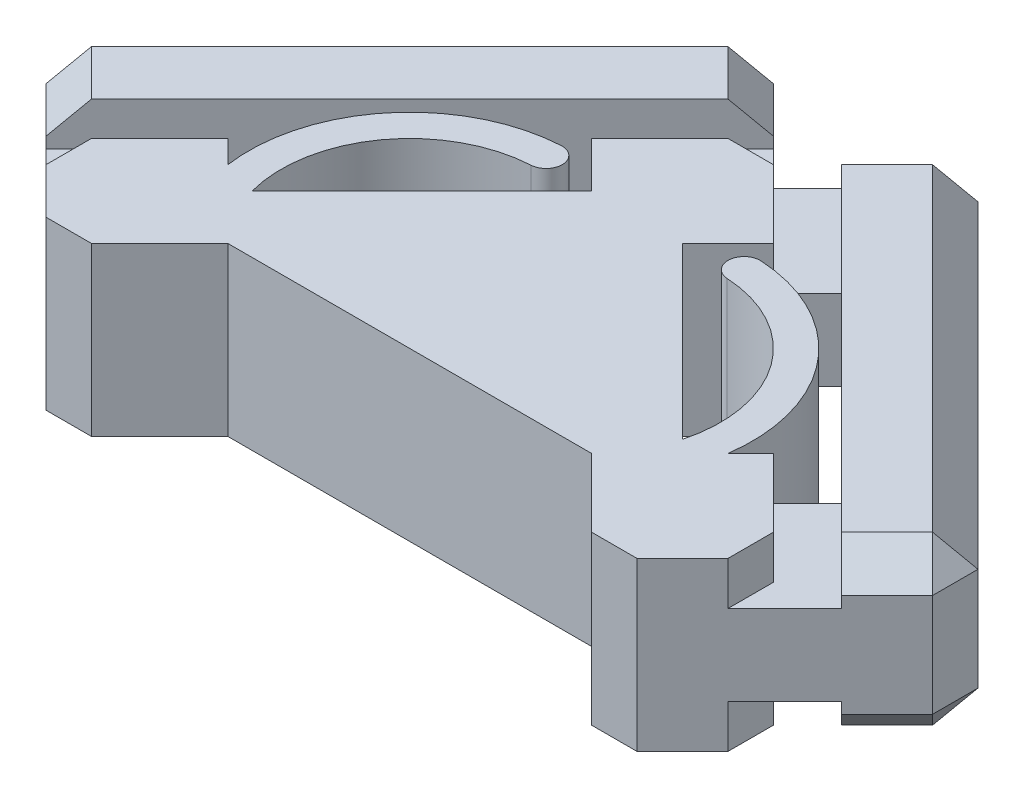
SolidWorks part; units mm, degrees
ref_plane "Front Plane" through (0, 0, 0) normal (0, 0, 1) x (1, 0, 0)
ref_plane "Top Plane" through (0, 0, 0) normal (0, 1, 0) x (1, 0, 0)
ref_plane "Right Plane" through (0, 0, 0) normal (1, 0, 0) x (0, 0, -1)
sketch "Sketch1" plane through (0, 0, 0) normal (0, 1, 0) x (1, 0, 0)
  line L0 (0, 0) -> (-2.8284, -2.8284)
  line L1 (-11.3137, -11.3137) -> (-8.4853, -14.1421)
  line L2 (-8.4853, -14.1421) -> (-5.6569, -11.3137)
  line L3 (-5.6569, -11.3137) -> (5.6569, -11.3137)
  line L4 (5.6569, -11.3137) -> (8.4853, -14.1421)
  line L5 (8.4853, -14.1421) -> (11.3137, -11.3137)
  line L6 (11.3137, -11.3137) -> (8.4853, -8.4853)
  line L7 (1.4142, -4.2426) -> (7.0711, -9.8995)
  line L8 (1.4142, -4.2426) -> (2.8284, -2.8284)
  line L9 (7.0711, -9.8995) -> (8.4853, -8.4853)
  line L10 (-8.4853, -8.4853) -> (-11.3137, -11.3137)
  line L11 (-7.0711, -9.8995) -> (-1.4142, -4.2426)
  line L12 (-7.0711, -9.8995) -> (-8.4853, -8.4853)
  line L13 (-1.4142, -4.2426) -> (-2.8284, -2.8284)
  line L15 (2.8284, -2.8284) -> (0, 0)
  dimension "D1" = 135
  dimension "D2" = 2
  dimension "D3" = 8
  dimension "D4" = 4
  dimension "D5" = 16
extrude "Boss-Extrude1" add sketch "Sketch1" along normal mid plane 5.2
ref_plane "Plane1" through (-5.6569, 0, 5.6569) normal (-0.7071, 0, 0.7071) x (0.7071, 0, 0.7071)
sketch "Sketch2" plane through (-11.3137, 0, 11.3137) normal (-0.7071, 0, 0.7071) x (0.7071, 0, 0.7071)
  line L0 (-1.5, -1.25) -> (-1.5, -2.6)
  line L1 (-4.5, 2.6) -> (-1.5, 2.6)
  line L2 (-4.5, 2.6) -> (-4.5, -2.6)
  line L3 (-4.5, -2.6) -> (-1.5, -2.6)
  line L4 (-1.5, 2.6) -> (-1.5, 1.25)
  line L5 (-1.5, 1.25) -> (0, 1.25)
  line L6 (0, 2.6) -> (0, -2.6) construction
  line L7 (-1.5, -1.25) -> (0, -1.25)
  line L8 (0, 1.25) -> (0, -1.25)
  line L9 (0, 2.6) -> (4, 2.6) construction
  line L10 (0, -2.6) -> (4, -2.6) construction
  point P6 (0, 0)
  dimension "D1" = 2.5
  dimension "D2" = 1.5
  dimension "D3" = 3
extrude "Boss-Extrude2" add sketch "Sketch2" against normal blind 4
mirror "Mirror1" about plane through (-5.6569, 0, 5.6569) normal (-0.7071, 0, 0.7071) of "Boss-Extrude2"
sketch "Sketch3" plane through (-2.8284, 0, 2.8284) normal (-0.7071, 0, 0.7071) x (0.7071, 0, 0.7071)
  line L1 (-4.5, 2.6) -> (-1.5, 2.6)
  line L2 (-4.5, 2.6) -> (-4.5, -2.6)
  line L3 (-4.5, -2.6) -> (-1.5, -2.6)
  line L4 (-1.5, 2.6) -> (-1.5, -2.6)
extrude "Boss-Extrude3" add sketch "Sketch3" along normal blind 8
sketch "Sketch4" plane through (0, 0, 0) normal (0, 1, 0) x (1, 0, 0)
  line L0 (-7.7782, -9.1924) -> (-7.0711, -9.8995)
  line L1 (-7.0711, -9.8995) -> (-6.6921, -9.5206)
  line L2 (-7.0711, -9.8995) -> (-8.4853, -8.4853) construction
  line L3 (-1.4142, -4.2426) -> (-7.0711, -9.8995) construction
  line L4 (-2.8284, -8.4853) -> (-6.7175, -4.5962) construction
  line L5 (-1.0607, 1.0607) -> (-12.3744, -10.253) construction
  line L6 (-2.8284, -2.8284) -> (-1.4142, -4.2426) construction
  arc A0 (-7.7782, -9.1924) -> (-3.1066, -3.493) centre (-2.8284, -8.4853) cw
  arc A1 (-3.1066, -3.493) -> (-3.051, -4.4915) centre (-3.0788, -3.9923) cw
  arc A2 (-6.6921, -9.5206) -> (-3.051, -4.4915) centre (-2.8284, -8.4853) cw
  point P16 (-6.7175, -4.5962)
  dimension "D1" = 5
  dimension "D3" = 1
  dimension "D2" = 0.5
  dimension "D4" = 2
extrude "Boss-Extrude4" add sketch "Sketch4" along normal mid plane 5.2
chamfer "Chamfer1" distance 1 angle 45 8 edges at (-8.8388, -2.6, 2.4749) (-2.1213, -2.6, -2.1213) (-3.182, 0, -3.182) (-2.1213, 2.6, -2.1213) (-8.8388, 2.6, 2.4749) (-13.435, -2.6, 9.1924) (-14.4957, 0, 8.1317) (-13.435, 2.6, 9.1924)
mirror "Mirror2" about plane through (0, 0, 0) normal (1, 0, 0) of "Boss-Extrude4", "Chamfer1", "Mirror1", "Boss-Extrude2", "Boss-Extrude1", "Boss-Extrude3"
chamfer "Chamfer2" distance 1 angle 45 8 edges at (0, -1.925, 0) (0, 1.925, 0) (8.4853, 0, 14.1421) (-8.4853, 0, 14.1421) (11.3137, -1.925, 11.3137) (11.3137, 1.925, 11.3137) (-11.3137, 1.925, 11.3137) (-11.3137, -1.925, 11.3137)
